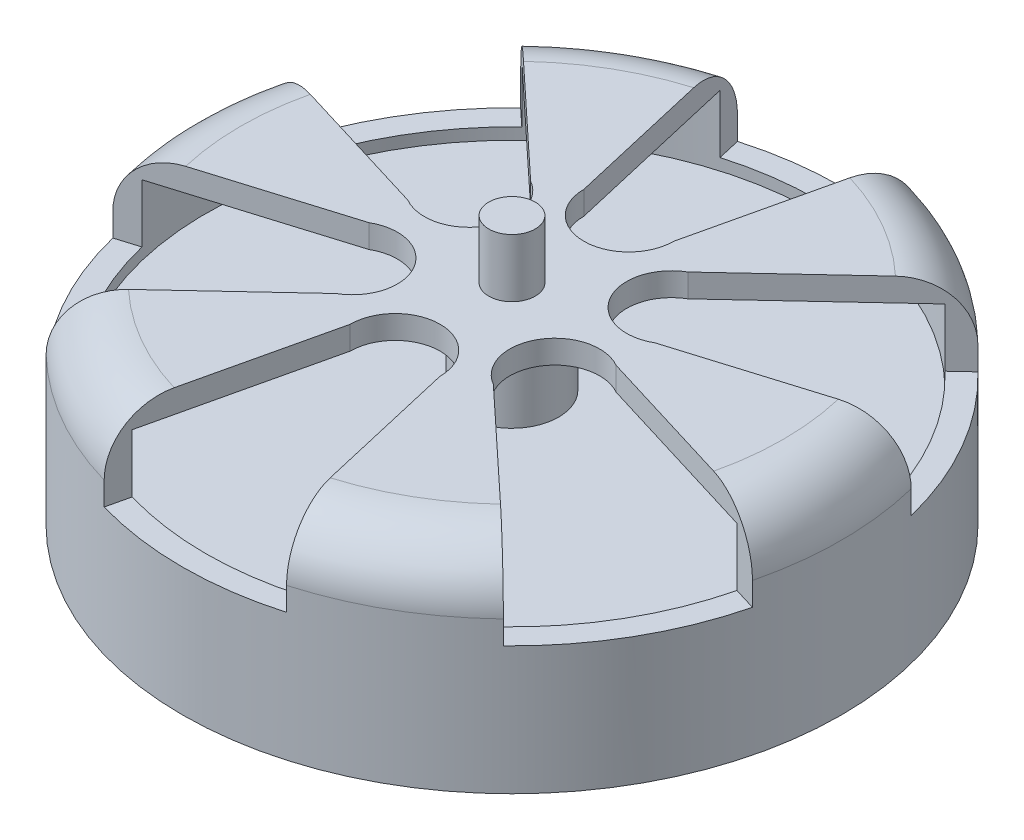
SolidWorks part; units mm, degrees
ref_plane "Front Plane" through (0, 0, 0) normal (0, 0, 1) x (1, 0, 0)
ref_plane "Top Plane" through (0, 0, 0) normal (0, 1, 0) x (1, 0, 0)
ref_plane "Right Plane" through (0, 0, 0) normal (1, 0, 0) x (0, 0, -1)
sketch "Sketch2" plane through (0, 0, 0) normal (0, 0, 1) x (1, 0, 0)
  line L0 (4, 22.15) -> (4, -7.85)
  line L2 (18.8, -7.85) -> (18.8, -0.85)
  line L3 (18.8, -0.85) -> (32.3, -0.85)
  line L4 (32.3, -0.85) -> (32.3, 17.15)
  line L5 (32.3, 17.15) -> (6, 17.15)
  line L6 (6, 17.15) -> (6, 22.15)
  line L7 (6, 22.15) -> (4, 22.15)
  line L11 (4, -7.85) -> (18.8, -7.85)
  line L12 (30.3, 15.15) -> (8, 15.15)
  line L13 (8, 15.15) -> (8, 9.15)
  line L14 (8, 9.15) -> (30.3, 9.15)
  line L15 (30.3, 9.15) -> (30.3, 15.15)
  dimension "D1" = 2
  dimension "D2" = 30
  dimension "D3" = 5
  dimension "D4" = 18
  dimension "D5" = 7
  dimension "D6" = 2
  dimension "D7" = 2
  dimension "D8" = 2
  dimension "D9" = 6
revolve "Revolve1" add sketch "Sketch2" angle 360 about L0
fillet "Fillet1" radius 5 1 edges at (4, 17.15, 28.3)
sketch "Sketch4" plane through (0, 17.15, 0) normal (0, 1, 0) x (1, 0, 0)
  line L0 (4, 0) -> (4, 32.0024) construction
  line L1 (4, 0) -> (4, -32.7348) construction
  line L2 (0.139, -10.0328) -> (-4.2364, -28.9466)
  line L5 (-4.2364, -28.9466) -> (12.2364, -28.9466)
  line L6 (7.861, -10.0328) -> (12.2364, -28.9466)
  arc A1 (7.861, -10.0328) -> (0.139, -10.0328) centre (4, -10.0328) ccw
  point P9 (4, -32.7348)
extrude "Cut-Extrude3" cut sketch "Sketch4" against normal blind 7
pattern_circular "CirPattern2" count 6 every 60 about axis through (4, 0, 0) along (0, 1, 0) of "Cut-Extrude3"
sketch "Sketch5" plane through (0, -7.85, 0) normal (0, -1, 0) x (1, 0, 0)
  line L0 (4, 28.3) -> (4, -28.3) construction
  line L1 (32.3, 0) -> (-24.3, 0) construction
  circle A0 centre (4, 0) radius 28.3 construction
  circle A1 centre (13.642, 0) radius 2
  point P10 (4, 0)
  dimension "D1" = 4
  dimension "D2" = 9.642
extrude "Cut-Extrude4" cut sketch "Sketch5" against normal blind 6
pattern_circular "CirPattern3" count 4 every 90 about axis through (3.8206, 0, 0) along (0, 1, 0) of "Cut-Extrude4"
thread "Thread1" pitch 1.5 start angle 0, offset 0, length 0, pitch 1.5, diameter 4
ref_plane "Plane2" through (1.8206, -1.85, 9.8214) normal (0, 0, 1) x (-1, 0, 0)
sketch "Thread Profile2" plane through (1.8206, -1.85, 9.8214) normal (0, 0, 1) x (-1, 0, 0)
  line L0 (0, 0) -> (0, 1.5) construction
  line L1 (0, 0) -> (0.8119, 0.4687)
  line L2 (0.8119, 0.4687) -> (0.8119, 0.6562)
  line L3 (0.8119, 0.6562) -> (0, 1.125)
  line L4 (0.8119, 0.5625) -> (0, 0.5625) construction
  line L11 (0, 0) -> (0, 1.125)
  point P2 (0, 0)
  dimension "Pitch" = 1.5
  dimension "Profile_Angle" = 60
  dimension "Profile_Land" = 0.1875
  dimension "Profile_Height" = 0.8119
thread "Thread2" pitch 1.5 profile "Thread Profile3" start angle 0, offset 0, length 0, pitch 1.5, diameter 4
ref_plane "Plane3" through (11.642, -1.85, 0) normal (0, 0, 1) x (-1, 0, 0)
sketch "Thread Profile3" plane through (11.642, -1.85, 0) normal (0, 0, 1) x (-1, 0, 0)
  line L0 (0, 0) -> (0, 1.5) construction
  line L1 (0, 0) -> (0.8119, 0.4687)
  line L2 (0.8119, 0.4687) -> (0.8119, 0.6562)
  line L3 (0.8119, 0.6562) -> (0, 1.125)
  line L4 (0.8119, 0.5625) -> (0, 0.5625) construction
  line L11 (0, 0) -> (0, 1.125)
  point P2 (0, 0)
  dimension "Pitch" = 1.5
  dimension "Profile_Angle" = 60
  dimension "Profile_Land" = 0.1875
  dimension "Profile_Height" = 0.8119
thread "Thread3" pitch 1.5 profile "Thread Profile4" start angle 0, offset 0, length 0, pitch 1.5, diameter 4
ref_plane "Plane4" through (-8.0007, -1.85, 0) normal (0, 0, 1) x (-1, 0, 0)
sketch "Thread Profile4" plane through (-8.0007, -1.85, 0) normal (0, 0, 1) x (-1, 0, 0)
  line L0 (0, 0) -> (0, 1.5) construction
  line L1 (0, 0) -> (0.8119, 0.4687)
  line L2 (0.8119, 0.4687) -> (0.8119, 0.6562)
  line L3 (0.8119, 0.6562) -> (0, 1.125)
  line L4 (0.8119, 0.5625) -> (0, 0.5625) construction
  line L11 (0, 0) -> (0, 1.125)
  point P2 (0, 0)
  dimension "Pitch" = 1.5
  dimension "Profile_Angle" = 60
  dimension "Profile_Land" = 0.1875
  dimension "Profile_Height" = 0.8119
thread "Thread4" pitch 1.5 profile "Thread Profile5" start angle 0, offset 0, length 0, pitch 1.5, diameter 4
ref_plane "Plane5" through (1.8206, -1.85, -9.8214) normal (0, 0, 1) x (-1, 0, 0)
sketch "Thread Profile5" plane through (1.8206, -1.85, -9.8214) normal (0, 0, 1) x (-1, 0, 0)
  line L0 (0, 0) -> (0, 1.5) construction
  line L1 (0, 0) -> (0.8119, 0.4687)
  line L2 (0.8119, 0.4687) -> (0.8119, 0.6562)
  line L3 (0.8119, 0.6562) -> (0, 1.125)
  line L4 (0.8119, 0.5625) -> (0, 0.5625) construction
  line L11 (0, 0) -> (0, 1.125)
  point P2 (0, 0)
  dimension "Pitch" = 1.5
  dimension "Profile_Angle" = 60
  dimension "Profile_Land" = 0.1875
  dimension "Profile_Height" = 0.8119
